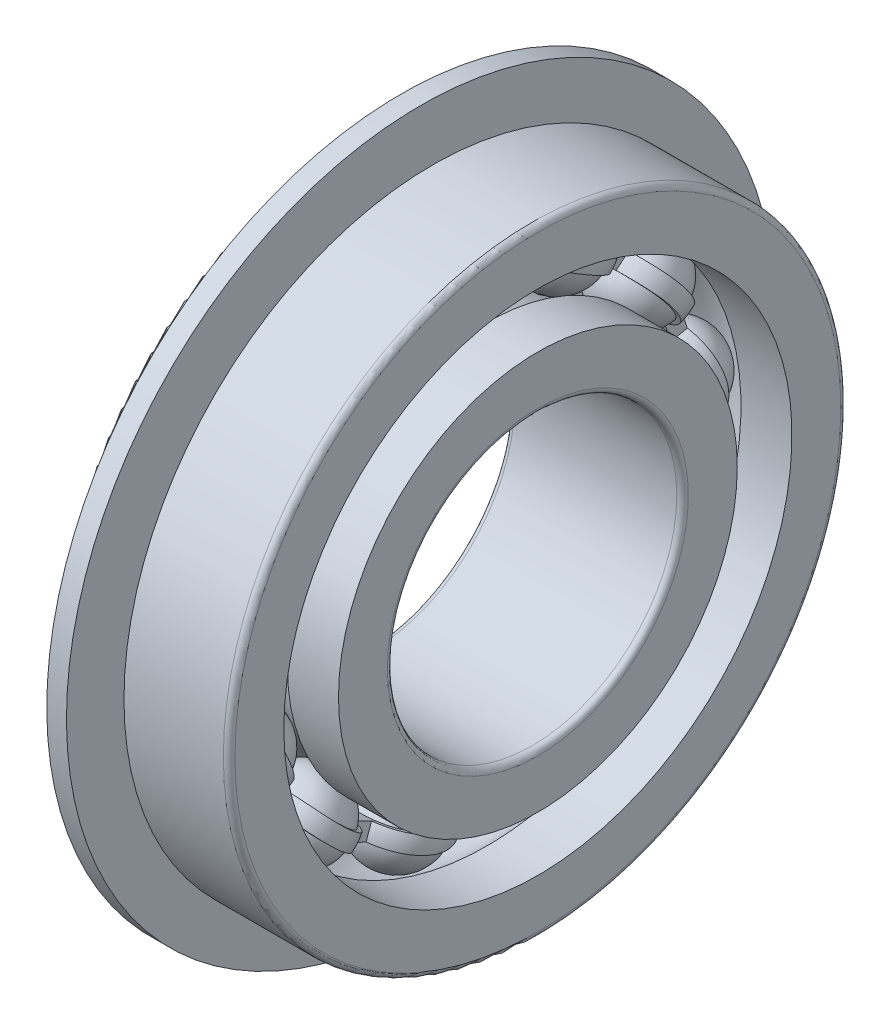
SolidWorks part; units mm, degrees
material "AISI 304"
ref_plane "前视基准面" through (0, 0, 0) normal (0, 0, 1) x (1, 0, 0)
ref_plane "上视基准面" through (0, 0, 0) normal (0, 1, 0) x (1, 0, 0)
ref_plane "右视基准面" through (0, 0, 0) normal (1, 0, 0) x (0, 0, -1)
sketch "尺寸草图" plane through (0, 0, 0) normal (0, 0, 1) x (1, 0, 0)
  line L0 (-19.9271, 0) -> (19.9271, 0) construction
  line L1 (0, 21.603) -> (0, -21.603) construction
  line L2 (-4.2, 16) -> (4.2, 16)
  line L3 (4.5, 15.7) -> (4.5, 13.4667)
  line L4 (-4.5, 15.7) -> (-4.5, 13.4667)
  line L5 (-4.2, 13.1667) -> (4.2, 13.1667)
  line L6 (-3.5, 11.75) -> (3.3577, 11.75) construction
  line L7 (-4.2, 10.3333) -> (4.2, 10.3333)
  line L8 (4.5, 10.0333) -> (4.5, 7.8)
  line L9 (4.2, 7.5) -> (-4.2, 7.5)
  line L10 (-4.5, 7.8) -> (-4.5, 10.0333)
  line L11 (0, 11.75) -> (0, 13.875) construction
  line L12 (-2.6, 16) -> (-2.6, 14.95)
  line L13 (-2.6, 14.95) -> (-0.95, 14.95)
  line L14 (-0.95, 14.95) -> (-0.95, 16)
  line L15 (-2.6, 16) -> (-2.6, 18.35)
  line L16 (-2.6, 18.35) -> (-1.58, 18.35)
  line L17 (-1.58, 18.35) -> (-1.58, 14.95)
  line L18 (-1.5, 0) -> (1.5, 0) construction
  circle A0 centre (0, 11.75) radius 2.125
  arc A1 (4.5, 13.4667) -> (4.2, 13.1667) centre (4.2, 13.4667) cw
  arc A2 (4.5, 10.0333) -> (4.2, 10.3333) centre (4.2, 10.0333) ccw
  arc A3 (-4.2, 10.3333) -> (-4.5, 10.0333) centre (-4.2, 10.0333) ccw
  arc A4 (-4.2, 13.1667) -> (-4.5, 13.4667) centre (-4.2, 13.4667) cw
  arc A5 (-4.2, 7.5) -> (-4.5, 7.8) centre (-4.2, 7.8) cw
  arc A6 (4.2, 7.5) -> (4.5, 7.8) centre (4.2, 7.8) ccw
  arc A7 (4.5, 15.7) -> (4.2, 16) centre (4.2, 15.7) ccw
  arc A8 (-4.2, 16) -> (-4.5, 15.7) centre (-4.2, 15.7) ccw
  arc A9 (-0.95, 15.35) -> (-1.35, 14.95) centre (-1.35, 15.35) cw
  point P7 (0, 0)
  point P25 (-4.5, 10.3333)
  point P28 (-4.5, 13.1667)
  point P31 (-4.5, 7.5)
  point P36 (4.5, 16)
  point P39 (-4.5, 16)
  dimension "D1" = 0.7083
  dimension "r1" = 0.3
  dimension "r0-" = 0.4
  dimension "r" = 0.3
  dimension "B" = 9
  dimension "D2" = 4.5
  dimension "D" = 32
  dimension "(d)" = 15
  dimension "D5" = 11.75
  dimension "D6" = 2.8333
  dimension "D7" = 2.8333
  dimension "a-" = 1.9
  dimension "D2-" = 36.7
  dimension "D1-" = 29.9
  dimension "b-" = 1.65
  dimension "f-" = 1.02
  dimension "g" = 3
sketch "草图2" plane through (0, 0, 0) normal (0, 0, 1) x (1, 0, 0)
  line L0 (-4.5, 13.4667) -> (-4.5, 13.1667)
  line L1 (-4.5, 13.1667) -> (-4.2, 13.1667)
  line L2 (4.2, 13.1667) -> (4.5, 13.1667)
  line L3 (4.5, 13.1667) -> (4.5, 13.4667)
  line L4 (-4.2, 10.3333) -> (-4.5, 10.3333)
  line L5 (-4.5, 10.3333) -> (-4.5, 10.0333)
  line L6 (4.2, 7.5) -> (-4.2, 7.5) construction
  line L7 (4.2, 10.3333) -> (4.5, 10.3333)
  line L8 (-4.5, 15.7) -> (-4.5, 13.4667) construction
  line L9 (-4.2, 13.1667) -> (4.2, 13.1667) construction
  line L10 (-4.2, 16) -> (4.2, 16) construction
  line L11 (4.5, 15.7) -> (4.5, 13.4667) construction
  line L12 (4.5, 10.0333) -> (4.5, 7.8) construction
  line L13 (-4.2, 10.3333) -> (4.2, 10.3333) construction
  line L14 (4.2, 7.5) -> (-4.2, 7.5)
  line L15 (-4.5, 7.8) -> (-4.5, 10.0333) construction
  line L16 (4.5, 10.3333) -> (4.5, 10.0333)
  line L18 (-3.5, 0) -> (3.5, 0) construction
  line L19 (-19.9271, 0) -> (19.9271, 0) construction
  line L20 (-4.5, 15.7) -> (-4.5, 13.4667)
  line L21 (-4.2, 13.1667) -> (-1.5839, 13.1667)
  line L22 (-4.2, 16) -> (4.2, 16)
  line L23 (4.5, 15.7) -> (4.5, 13.4667)
  line L24 (4.5, 10.0333) -> (4.5, 7.8)
  line L25 (-4.2, 10.3333) -> (-1.5839, 10.3333)
  line L26 (-4.5, 7.8) -> (-4.5, 10.0333)
  line L27 (1.5839, 13.1667) -> (4.2, 13.1667)
  line L28 (1.5839, 10.3333) -> (4.2, 10.3333)
  circle A0 centre (0, 11.75) radius 2.125 construction
  arc A1 (1.5839, 13.1667) -> (-1.5839, 13.1667) centre (0, 11.75) ccw
  arc A2 (-1.5839, 10.3333) -> (1.5839, 10.3333) centre (0, 11.75) ccw
  arc A3 (-4.2, 16) -> (-4.5, 15.7) centre (-4.2, 15.7) ccw construction
  arc A4 (-4.5, 13.4667) -> (-4.2, 13.1667) centre (-4.2, 13.4667) ccw construction
  arc A5 (4.5, 15.7) -> (4.2, 16) centre (4.2, 15.7) ccw construction
  arc A6 (4.2, 13.1667) -> (4.5, 13.4667) centre (4.2, 13.4667) ccw construction
  arc A7 (4.5, 10.0333) -> (4.2, 10.3333) centre (4.2, 10.0333) ccw construction
  arc A8 (4.2, 7.5) -> (4.5, 7.8) centre (4.2, 7.8) ccw construction
  arc A9 (-4.2, 10.3333) -> (-4.5, 10.0333) centre (-4.2, 10.0333) ccw construction
  arc A10 (-4.5, 7.8) -> (-4.2, 7.5) centre (-4.2, 7.8) ccw construction
  arc A11 (-4.2, 16) -> (-4.5, 15.7) centre (-4.2, 15.7) ccw
  arc A12 (-4.5, 13.4667) -> (-4.2, 13.1667) centre (-4.2, 13.4667) ccw construction
  arc A13 (4.5, 15.7) -> (4.2, 16) centre (4.2, 15.7) ccw
  arc A14 (4.2, 13.1667) -> (4.5, 13.4667) centre (4.2, 13.4667) ccw construction
  arc A15 (4.5, 10.0333) -> (4.2, 10.3333) centre (4.2, 10.0333) ccw construction
  arc A16 (4.2, 7.5) -> (4.5, 7.8) centre (4.2, 7.8) ccw
  arc A17 (-4.2, 10.3333) -> (-4.5, 10.0333) centre (-4.2, 10.0333) ccw construction
  arc A18 (-4.5, 7.8) -> (-4.2, 7.5) centre (-4.2, 7.8) ccw
revolve "旋转1" add sketch "草图2" angle 360 about L18 region at (0, 14.6545, 0) region at (0, 8.8455, 0)
sketch "草图5" plane through (0, 0, 0) normal (0, 0, 1) x (1, 0, 0)
  line L1 (-0.6375, 11.325) -> (0.6375, 11.325)
  line L2 (-0.6375, 11.325) -> (-0.6375, 12.175)
  line L3 (-0.6375, 12.175) -> (0.6375, 12.175)
  line L4 (0.6375, 11.325) -> (0.6375, 12.175)
  line L5 (-0.6375, 11.325) -> (0.6375, 12.175) construction
  line L6 (-0.6375, 12.175) -> (0.6375, 11.325) construction
  circle A0 centre (0, 11.75) radius 2.125 construction
  circle A1 centre (0, 11.75) radius 2.125 construction
  point P0 (0, 11.75)
  dimension "D1" = 1.275
  dimension "D2" = 0.85
revolve "旋转3" add sketch "草图5" angle 360 about L0
sketch "草图3" plane through (0, 0, 0) normal (0, 0, 1) x (1, 0, 0)
  line L1 (-2.3375, 11.75) -> (2.3375, 11.75)
  circle A0 centre (0, 11.75) radius 2.125 construction
  circle A1 centre (0, 11.75) radius 2.125 construction
  arc A2 (2.3375, 11.75) -> (-2.3375, 11.75) centre (0, 11.75) ccw
  dimension "D2" = 4.675
revolve "旋转2" add sketch "草图3" angle 360 about L1 region at (0, 12.7421, 0)
ref_axis "基准轴1" through (-3.85, 0, 0) along (1, 0, 0)
pattern_circular "阵列(圆周)5" count 13 over 360 about axis through (-3.85, 0, 0) along (1, 0, 0) of bodies 103
sketch "草图6" plane through (0, 0, 0) normal (0, 0, 1) x (1, 0, 0)
  line L0 (-2.2985, 12.175) -> (2.2985, 12.175)
  line L1 (-3.5, 11.75) -> (4.5, 11.75) construction
  line L3 (-2.2985, 11.325) -> (2.2985, 11.325)
  line L4 (4.5, -15.7) -> (4.5, 15.7) construction
  arc A0 (-2.2985, 11.325) -> (2.2985, 11.325) centre (0, 11.75) ccw
  circle A1 centre (0, 11.75) radius 2.125 construction
  circle A2 centre (0, 11.75) radius 2.125 construction
  arc A3 (2.2985, 12.175) -> (-2.2985, 12.175) centre (0, 11.75) ccw
  dimension "D1" = 4.675
  dimension "D3" = 0.425
  dimension "D4" = 0.425
revolve "切除-旋转1" cut sketch "草图6" angle 360 about L0
sketch "草图7" plane through (0, 0, 0) normal (0, 0, 1) x (1, 0, 0)
  line L0 (-2.125, 11.75) -> (2.125, 11.75)
  line L1 (-4.5, 0) -> (4.5, 0) construction
  line L2 (-4.5, 15.7) -> (-4.5, -15.7) construction
  line L3 (4.5, -15.7) -> (4.5, 15.7) construction
  circle A0 centre (0, 11.75) radius 2.125 construction
  arc A1 (2.125, 11.75) -> (-2.125, 11.75) centre (0, 11.75) ccw
revolve "旋转4" add sketch "草图7" angle 360 about L0
pattern_circular "阵列(圆周)2" count 13 over 360 about axis through (-3.85, 0, 0) along (1, 0, 0) of "旋转4"
sketch "草图8" plane through (0, 0, 0) normal (0, 0, 1) x (1, 0, 0)
  line L0 (-2.6, 14.95) -> (-0.95, 14.95) construction
  line L2 (-2.6, 14.95) -> (-0.95, 14.95)
  line L3 (-0.95, 14.95) -> (-0.95, 16)
  line L4 (-2.6, 14.95) -> (-2.6, 16)
  line L5 (-2.6, 16) -> (-0.95, 16)
  line L6 (-0.95, 14.95) -> (-0.95, 16) construction
revolve "切除-旋转2" cut sketch "草图8" angle 360 about L0
sketch "草图9" plane through (0, 0, 0) normal (0, 0, 1) x (1, 0, 0)
  line L0 (-2.6, 18.35) -> (-1.58, 18.35) construction
  line L1 (-1.58, 18.35) -> (-1.58, 14.95) construction
  line L2 (-2.6, 16) -> (-2.6, 18.35) construction
  line L3 (-2.6, 16) -> (-2.6, 14.95) construction
  line L4 (-2.6, 14.95) -> (-0.95, 14.95) construction
  line L5 (-2.6, 18.35) -> (-1.58, 18.35)
  line L6 (-1.58, 18.35) -> (-1.58, 14.95)
  line L7 (-2.6, 16) -> (-2.6, 18.35)
  line L8 (-2.6, 16) -> (-2.6, 14.95)
  line L9 (-2.6, 14.95) -> (-1.58, 14.95)
revolve "旋转5" add sketch "草图9" angle 360 about L0
sketch "草图11" plane through (0, 0, 0) normal (1, 0, 0) x (0, 0, -1)
  line L0 (0, 21.603) -> (0, -21.603) construction
  line L2 (-1.5, -14.8746) -> (-1.5, -22.02)
  line L3 (-1.5, -22.02) -> (1.5, -22.02)
  line L4 (1.5, -14.8746) -> (1.5, -22.02)
  arc A0 (-1.5, -14.8746) -> (1.5, -14.8746) centre (0, 0) ccw
  point P7 (0, -22.02)
  dimension "D1" = 3
  dimension "D2" = 22.02
extrude "切除-拉伸1" cut sketch "草图11" against normal up to vertex from vertex up to point (-2.6, 18.35, 0) starting at point (-1.58, 18.35, 0)
fillet "圆角1" radius 0.4 2 edges at (-0.95, 0, 14.95) (-2.6, -14.95, 0)
